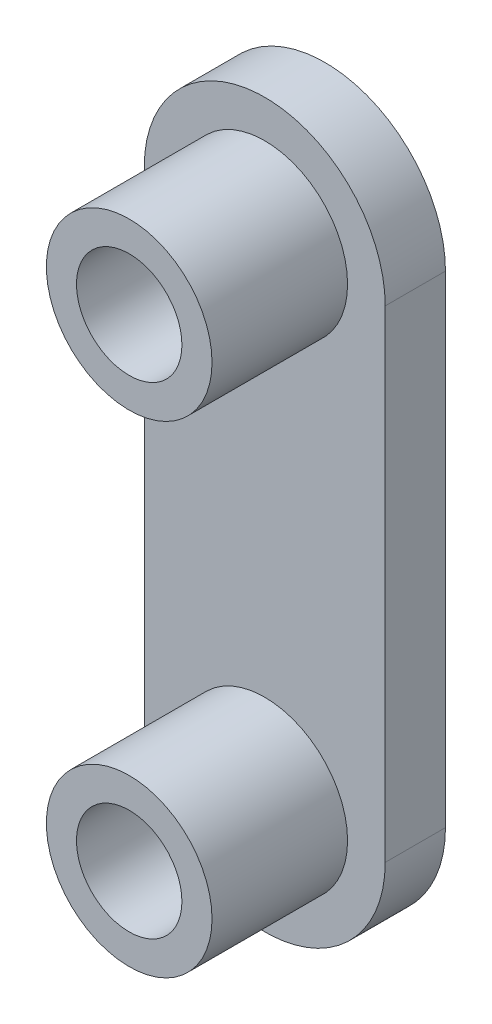
SolidWorks part; units mm, degrees
ref_plane "Front Plane" through (0, 0, 0) normal (0, 0, 1) x (1, 0, 0)
ref_plane "Top Plane" through (0, 0, 0) normal (0, 1, 0) x (1, 0, 0)
ref_plane "Right Plane" through (0, 0, 0) normal (1, 0, 0) x (0, 0, -1)
sketch "Sketch1" plane through (0, 0, 0) normal (0, 0, 1) x (1, 0, 0)
  line L0 (0, 0) -> (0, -16) construction
  line L1 (-4, 0) -> (-4, -16)
  line L2 (4, 0) -> (4, -16)
  circle A0 centre (0, 0) radius 4
  circle A1 centre (0, -16) radius 4
  circle A2 centre (0, 0) radius 1.75
  circle A3 centre (0, 0) radius 2.75
  circle A4 centre (0, -16) radius 1.75
  circle A5 centre (0, -16) radius 2.75
  dimension "D1" = 8
  dimension "D2" = 8
  dimension "D4" = 3.5
  dimension "D5" = 5.5
  dimension "D6" = 3.5
  dimension "D7" = 5.5
  dimension "D3" = 16
extrude "Boss-Extrude1" add sketch "Sketch1" against normal blind 2 contours A0 L0 A1 L2 | L0 A0 L1 A1 | A0 | A1 region at (2.1955, -8, 0) region at (-2.1955, -8, 0)
extrude "Boss-Extrude2" add sketch "Sketch1<3>" along normal blind 4.5 contours A2 A3 | A5 A4 region at (-2.6722, 0, 0) region at (-2.6722, -16, 0)
sketch "Sketch1<3>" plane through (0, 0, 0) normal (0, 0, 1) x (1, 0, 0) same geometry as "Sketch1"
